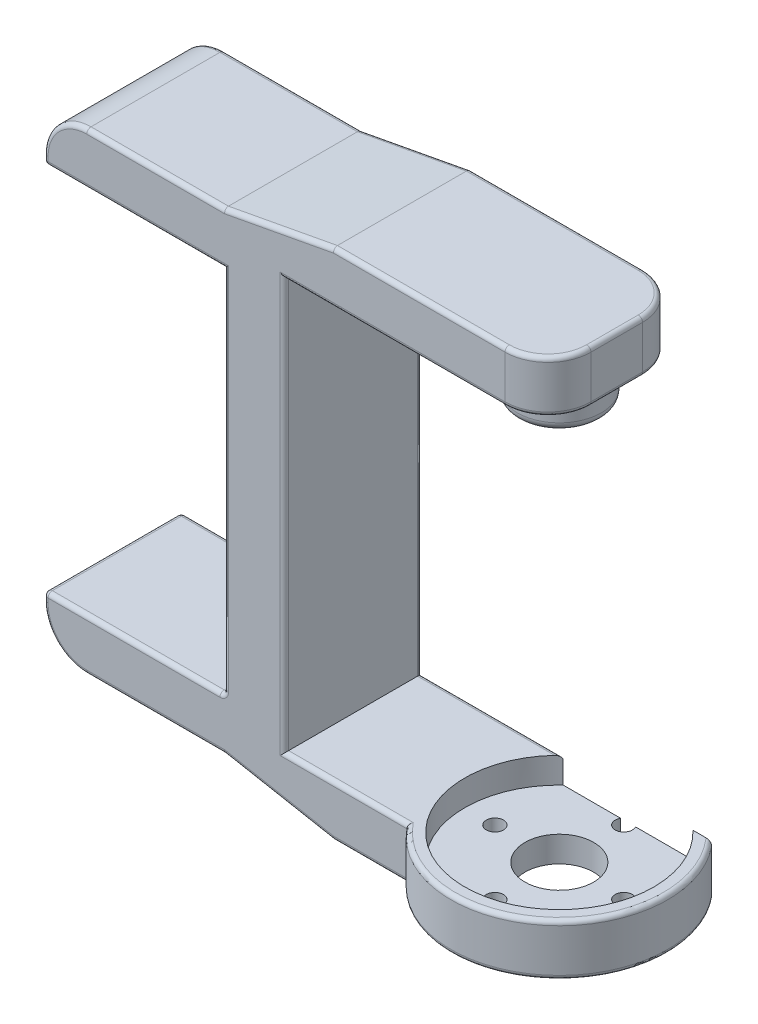
SolidWorks part; units mm, degrees
note: The reader was unsure of these and kept them because the rebuilt part matched: shared geometry of "Sketch3<3>", "Sketch3<4>", "Sketch4<3>".
material "ABS"
ref_plane "Front Plane" through (0, 0, 0) normal (0, 0, 1) x (1, 0, 0)
ref_plane "Top Plane" through (0, 0, 0) normal (0, 1, 0) x (1, 0, 0)
ref_plane "Right Plane" through (0, 0, 0) normal (1, 0, 0) x (0, 0, -1)
sketch "Sketch1" plane through (0, 0, 0) normal (0, 0, 1) x (1, 0, 0)
  line L0 (0, 49) -> (21, 49)
  line L1 (0, 0) -> (21, 0)
  line L3 (0, 43) -> (21, 43)
  line L4 (21, 0) -> (21, 43)
  line L5 (0, -6) -> (21, -6)
  line L6 (28, 0) -> (28, 43)
  line L8 (28, 45.373) -> (28, 43)
  line L9 (28, 0) -> (28, -2.373)
  line L11 (0, -6) -> (0, 0)
  line L12 (0, 43) -> (0, 49)
  line L13 (21, 49) -> (33.6799, 51.373)
  line L14 (0, 21.5) -> (28, 21.5) construction
  line L15 (33.6799, 51.373) -> (58.6799, 51.373)
  line L16 (33.6799, 45.373) -> (58.6799, 45.373)
  line L17 (33.6799, 45.373) -> (28, 45.373)
  line L18 (58.6799, 45.373) -> (58.6799, 51.373)
  line L19 (21, -6) -> (33.6799, -8.373)
  line L20 (33.6799, -2.373) -> (28, -2.373)
  line L21 (58.6799, -2.373) -> (58.6799, -8.373)
  line L22 (33.6799, -8.373) -> (58.6799, -8.373)
  line L23 (33.6799, -2.373) -> (58.6799, -2.373)
  dimension "D1" = 43
  dimension "D2" = 21
  dimension "D6" = 12.9
  dimension "D7" = 169.4
  dimension "D8" = 25
  dimension "D9" = 6
  dimension "D3" = 6
  dimension "D4" = 6
extrude "Boss-Extrude1" add sketch "Sketch1" along normal blind 16
sketch "Sketch3" plane through (0, -2.373, 0) normal (0, 1, 0) x (1, 0, 0)
  line L0 (58.6799, 0) -> (28, 0) construction
  line L1 (58.6799, 0) -> (42.2655, 0)
  line L2 (48, -8) -> (41, -8)
  line L3 (58.6799, 0) -> (61.7345, 0)
  arc A0 (44.4502, 0) -> (59.5498, 0) centre (52, -8) ccw
  circle A1 centre (52, -8) radius 4
  arc A10 (42.2655, 0) -> (61.7345, 0) centre (52, -8) ccw
  circle A11 centre (52, -8) radius 12.6 construction
  circle A12 centre (52, -8) radius 11 construction
  circle A16 centre (44.5, -8) radius 1
  arc A17 (51.134, 0) -> (52.866, 0) centre (52, -0.5) ccw
  circle A18 centre (59.5, -8) radius 1
  circle A19 centre (52, -15.5) radius 1
  point P18 (52, -8)
  point P26 (52, -8)
  dimension "D2" = 22
  dimension "D3" = 8
  dimension "D5" = 4
  dimension "D1" = 2
  dimension "D4" = 1.6
extrude "Boss-Extrude2" add sketch "Sketch3" against normal up to surface (6 mm away)
extrude "Cut-Extrude1" cut sketch "Sketch3<3>" against normal blind 3
sketch "Sketch3<3>" plane through (0, -2.373, 0) normal (0, 1, 0) x (1, 0, 0) same geometry as "Sketch3"
extrude "Cut-Extrude2" cut sketch "Sketch3<4>" against normal mid plane 13
sketch "Sketch3<4>" plane through (0, -2.373, 0) normal (0, 1, 0) x (1, 0, 0) same geometry as "Sketch3"
sketch "Sketch4" plane through (0, 45.373, 0) normal (0, -1, 0) x (1, 0, 0)
  line L0 (28, 8) -> (52, 8) construction
  line L4 (28, 16) -> (28, 0) construction
  circle A0 centre (52, 8) radius 4.9
  circle A1 centre (52, 8) radius 1
  dimension "D2" = 9.8
  dimension "D3" = 2
  dimension "D1" = 24
extrude "Boss-Extrude3" add sketch "Sketch4" along normal blind 4
extrude "Boss-Extrude4" add sketch "Sketch4<3>" along normal blind 5
sketch "Sketch4<3>" plane through (0, 45.373, 0) normal (0, -1, 0) x (1, 0, 0) same geometry as "Sketch4"
fillet "Fillet1" radius 0.8 1 edges at (52, 40.373, 7)
fillet "Fillet2" radius 1 1 edges at (52, 41.373, 3.1)
fillet "Fillet3" radius 5 2 edges at (58.6799, 48.373, 16) (58.6799, 48.373, 0)
fillet "Fillet4" radius 5 2 edges at (0, -6, 8) (0, 49, 8)
fillet "Fillet5" radius 0.5 42 edges at (43.6799, 51.373, 16) (57.2154, 51.373, 14.5355) (58.6799, 51.373, 8) (57.2154, 51.373, 1.4645) (0, 43.5, 16) (1.4645, 47.5355, 16) (0, 43.5, 0) (1.4645, 47.5355, 0) (0, -0.5, 16) (1.4645, -4.5355, 16) (0, -0.5, 0) (1.4645, -4.5355, 0) (40.8399, 45.373, 16) (57.2154, 45.373, 14.5355) (58.6799, 45.373, 8) (57.2154, 45.373, 1.4645) (43.6799, 51.373, 0) (27.3399, 50.1865, 16) (13, 49, 16) (13, 49, 0) (27.3399, 50.1865, 0) (13, -6, 16) (13, -6, 0) (27.3399, -7.1865, 0) (27.3399, -7.1865, 16) (37.9727, -8.373, 16) (60, -8.373, 17.7345) (60, -2.373, 17.7345) (35.1328, -2.373, 16) (28, 21.5, 16) (40.8399, 45.373, 0) (28, 21.5, 0) (36.2251, -2.373, 0) (0, 43, 8) (0, 0, 8) (21, 0, 8) (10.5, 0, 16) (21, 21.5, 16) (10.5, 43, 16) (10.5, 43, 0) (21, 21.5, 0) (10.5, 0, 0)
ref_plane "Plane1" through (0, 0, -10) normal (0, 0, -1) x (-1, 0, 0)
